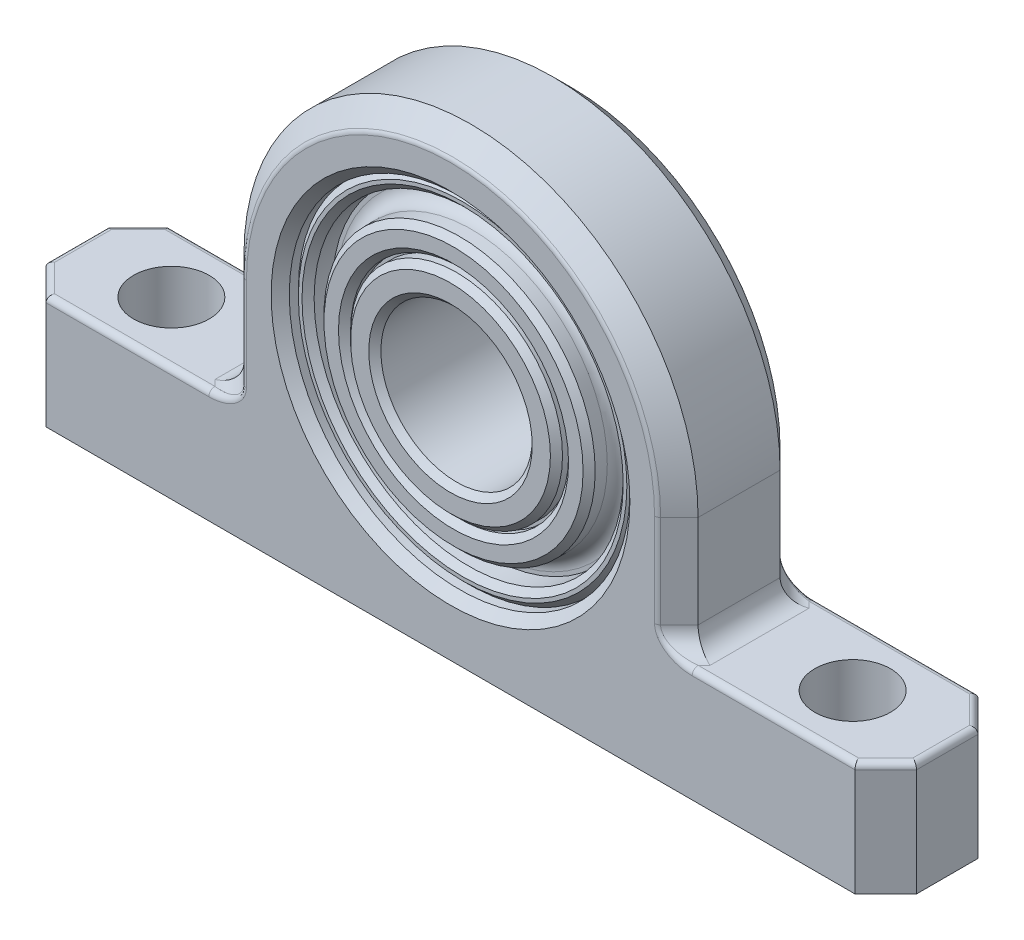
SolidWorks part; units mm, degrees
ref_plane "Front Plane" through (0, 0, 0) normal (0, 0, 1) x (1, 0, 0)
ref_plane "Top Plane" through (0, 0, 0) normal (0, 1, 0) x (1, 0, 0)
ref_plane "Right Plane" through (0, 0, 0) normal (1, 0, 0) x (0, 0, -1)
sketch "Sketch1" plane through (0, 0, 0) normal (0, 0, 1) x (1, 0, 0)
  line L0 (9.525, 0) -> (9.525, -4.7625)
  line L1 (9.525, -4.7625) -> (18.2562, -4.7625)
  line L2 (18.2562, -4.7625) -> (18.2562, -9.525)
  line L3 (18.2562, -9.525) -> (-18.2563, -9.525)
  line L4 (-18.2563, -9.525) -> (-18.2563, -4.7625)
  line L5 (-18.2563, -4.7625) -> (-9.525, -4.7625)
  line L6 (-9.525, -4.7625) -> (-9.525, 0)
  circle A0 centre (0, 0) radius 3.175
  arc A1 (9.525, 0) -> (-9.525, 0) centre (0, 0) ccw
  circle A2 centre (0, 0) radius 7.1438
  point P12 (0, 7.1438)
  point P13 (0, 3.175)
  dimension "D1" = 14.2875
  dimension "shaft dia" = 6.35
  dimension "I" = 19.05
  dimension "G" = 4.7625
  dimension "B" = 36.5125
  dimension "A" = 9.525
sketch "Sketch2" plane through (0, 0, 0) normal (0, 1, 0) x (1, 0, 0)
  line L0 (0, 2.5797) -> (0, -2.5797) construction
  line L1 (-14.2875, 0) -> (14.2875, 0) construction
  circle A0 centre (14.2875, 0) radius 1.5875
  circle A1 centre (-14.2875, 0) radius 1.5875
  dimension "F" = 3.175
  dimension "E" = 5.1594
  dimension "C" = 28.575
sketch "Sketch3" plane through (0, 0, 0) normal (0, 0, 1) x (1, 0, 0)
  line L0 (9.525, 0) -> (9.525, -4.7625) construction
  line L1 (18.2562, -4.7625) -> (18.2562, -9.525) construction
  line L2 (9.525, -4.7625) -> (18.2562, -4.7625) construction
  line L3 (18.2562, -9.525) -> (-18.2563, -9.525) construction
  line L4 (-18.2563, -9.525) -> (-18.2563, -4.7625) construction
  line L5 (-18.2563, -4.7625) -> (-9.525, -4.7625) construction
  line L6 (-9.525, -4.7625) -> (-9.525, 0) construction
  line L7 (9.525, 0) -> (9.525, -4.7625)
  line L8 (18.2562, -4.7625) -> (18.2562, -9.525)
  line L9 (9.525, -4.7625) -> (18.2562, -4.7625)
  line L10 (18.2562, -9.525) -> (-18.2563, -9.525)
  line L11 (-18.2563, -9.525) -> (-18.2563, -4.7625)
  line L12 (-18.2563, -4.7625) -> (-9.525, -4.7625)
  line L13 (-9.525, -4.7625) -> (-9.525, 0)
  arc A0 (9.525, 0) -> (-9.525, 0) centre (0, 0) ccw construction
  circle A1 centre (0, 0) radius 7.1438 construction
  arc A2 (9.525, 0) -> (-9.525, 0) centre (0, 0) ccw
  circle A3 centre (0, 0) radius 7.1438
extrude "Extrude1" add sketch "Sketch3" along normal up to vertex (2.5797 mm away) and the other way up to vertex (2.5797 mm away) up to point (0, 0, 2.5797) other way up to point (0, 0, -2.5797)
sketch "Sketch4" plane through (0, -4.7625, 0) normal (0, 1, 0) x (1, 0, 0)
  line L0 (-18.2563, 2.5797) -> (-18.2563, 1.2898)
  line L1 (-18.2563, -2.5797) -> (-18.2563, 2.5797) construction
  line L2 (-18.2563, 1.2898) -> (-16.9664, 2.5797)
  line L3 (-9.525, 2.5797) -> (-18.2563, 2.5797) construction
  line L4 (-16.9664, 2.5797) -> (-18.2563, 2.5797)
  line L5 (0, 0) -> (0, 2.5797) construction
  line L6 (0, 0) -> (-14.2875, 0) construction
  line L7 (16.9664, 2.5797) -> (18.2563, 2.5797)
  line L8 (18.2563, 1.2898) -> (16.9664, 2.5797)
  line L9 (18.2563, 2.5797) -> (18.2563, 1.2898)
  line L10 (18.2563, -2.5797) -> (18.2563, -1.2898)
  line L11 (18.2563, -1.2898) -> (16.9664, -2.5797)
  line L12 (16.9664, -2.5797) -> (18.2563, -2.5797)
  line L13 (-16.9664, -2.5797) -> (-18.2563, -2.5797)
  line L14 (-18.2563, -1.2898) -> (-16.9664, -2.5797)
  line L15 (-18.2563, -2.5797) -> (-18.2563, -1.2898)
  circle A0 centre (-14.2875, 0) radius 1.5875 construction
  circle A1 centre (14.2875, 0) radius 1.5875 construction
  circle A2 centre (-14.2875, 0) radius 1.5875
  circle A3 centre (14.2875, 0) radius 1.5875
  dimension "D1" = 45
  dimension "D2" = 1.2898
extrude "Cut-Extrude1" cut sketch "Sketch4" against normal through all
chamfer "Chamfer3" distance 0.8599 angle 45 6 edges at (-9.525, -2.3812, -2.5797) (0, 9.525, -2.5797) (9.525, -2.3812, -2.5797) (-9.525, -2.3812, 2.5797) (0, 9.525, 2.5797) (9.525, -2.3812, 2.5797)
fillet "Fillet6" radius 0.8599 6 edges at (9.525, -4.7625, 0) (9.0951, -4.7625, -2.1497) (9.0951, -4.7625, 2.1497) (-9.0951, -4.7625, -2.1497) (-9.0951, -4.7625, 2.1497) (-9.525, -4.7625, 0)
fillet "Fillet7" radius 0.254 20 edges at (13.4238, -4.7625, -2.5797) (9.0213, -4.5106, -2.5797) (8.6651, -1.9513, -2.5797) (0, 8.6651, -2.5797) (-8.6651, -1.9513, -2.5797) (-9.0213, -4.5106, -2.5797) (13.4238, -4.7625, 2.5797) (9.0213, -4.5106, 2.5797) (8.6651, -1.9513, 2.5797) (0, 8.6651, 2.5797) (-8.6651, -1.9513, 2.5797) (-9.0213, -4.5106, 2.5797) (17.6113, -4.7625, 1.9348) (18.2563, -4.7625, 0) (17.6113, -4.7625, -1.9348) (-13.4238, -4.7625, -2.5797) (-17.6113, -4.7625, -1.9348) (-18.2563, -4.7625, 0) (-17.6113, -4.7625, 1.9348) (-13.4238, -4.7625, 2.5797)
chamfer "Chamfer4" distance 0.381 angle 45 2 edges at (7.1438, 0, -2.5797) (7.1438, 0, 2.5797)
sketch "Sketch5" plane through (0, 0, 0) normal (1, 0, 0) x (0, 0, -1)
  line L0 (-2.0717, 6.4823) -> (-1.0557, 6.4823)
  line L3 (0, 0) -> (-2.5797, 0) construction
  line L4 (2.5797, 4.445) -> (2.5797, 3.175)
  line L5 (-1.0557, 6.4823) -> (-1.0557, 5.6885)
  line L6 (-1.0557, 5.6885) -> (-2.4527, 5.6885)
  line L7 (-1.9447, 4.445) -> (-1.9447, 4.572)
  line L8 (-2.5797, 3.175) -> (2.5797, 3.175)
  line L9 (-1.9447, 4.445) -> (-2.5797, 4.445)
  line L10 (-2.0717, 7.1438) -> (2.0717, 7.1438)
  line L12 (-2.5797, 4.445) -> (-2.5797, 3.175)
  line L13 (-2.0717, 7.1438) -> (-2.0717, 6.4823)
  line L14 (-2.5797, -9.525) -> (-2.5797, -5.0165) construction
  line L15 (-1.9447, 4.572) -> (-2.4527, 4.572)
  line L16 (-2.4527, 4.572) -> (-2.4527, 5.6885)
  line L17 (0, 7.1438) -> (0, 9.525) construction
  line L18 (0, 9.525) -> (0, 0) construction
  line L19 (2.4527, 4.572) -> (2.4527, 5.6885)
  line L20 (1.9447, 4.572) -> (2.4527, 4.572)
  line L21 (2.0717, 7.1438) -> (2.0717, 6.4823)
  line L22 (1.9447, 4.445) -> (2.5797, 4.445)
  line L23 (1.9447, 4.445) -> (1.9447, 4.572)
  line L24 (1.0557, 5.6885) -> (2.4527, 5.6885)
  line L25 (1.0557, 6.4823) -> (1.0557, 5.6885)
  line L26 (2.0717, 6.4823) -> (1.0557, 6.4823)
  line L27 (1.7198, 9.525) -> (-1.7198, 9.525) construction
  dimension "D1" = 3.9688
  dimension "D2" = 0.6615
  dimension "D3" = 0.7938
  dimension "D4" = 8.89
  dimension "D5" = 0.635
  dimension "D6" = 1.016
  dimension "D7" = 0.127
  dimension "D8" = 0.127
  dimension "D9" = 0.508
revolve "Revolve1" add sketch "Sketch5" angle 360 about L0
chamfer "Chamfer5" distance 0.254 angle 45 12 edges at (-3.175, 0, -2.5797) (-4.445, 0, -2.5797) (-4.445, 0, 2.5797) (-3.175, 0, 2.5797) (-4.572, 0, -2.4527) (-5.6885, 0, -2.4527) (-5.6885, 0, 2.4527) (-4.572, 0, 2.4527) (-6.4823, 0, -2.0717) (-7.1438, 0, -2.0717) (-7.1437, 0, 2.0717) (-6.4823, 0, 2.0717)
fillet "Fillet8" radius 0.635 2 edges at (-5.6885, 0, -1.0557) (-5.6885, 0, 1.0557)
equation "\"D1@Sketch1\"=\"I@Sketch1\"*.75"
equation "\"D2@Sketch4\" = \"E@Sketch2\"/4"
equation "\"D1@Chamfer3\"=\"E@Sketch2\"/6"
equation "\"D1@Fillet6\"=\"D1@Chamfer3\""
equation "\"D2@Sketch5\"=\"D1@Sketch5\"/6"
equation "\"D3@Sketch5\"=\"D2@Sketch5\"*1.2"
equation "\"D4@Sketch5\"=\"shaft dia@Sketch1\"*1.4"
